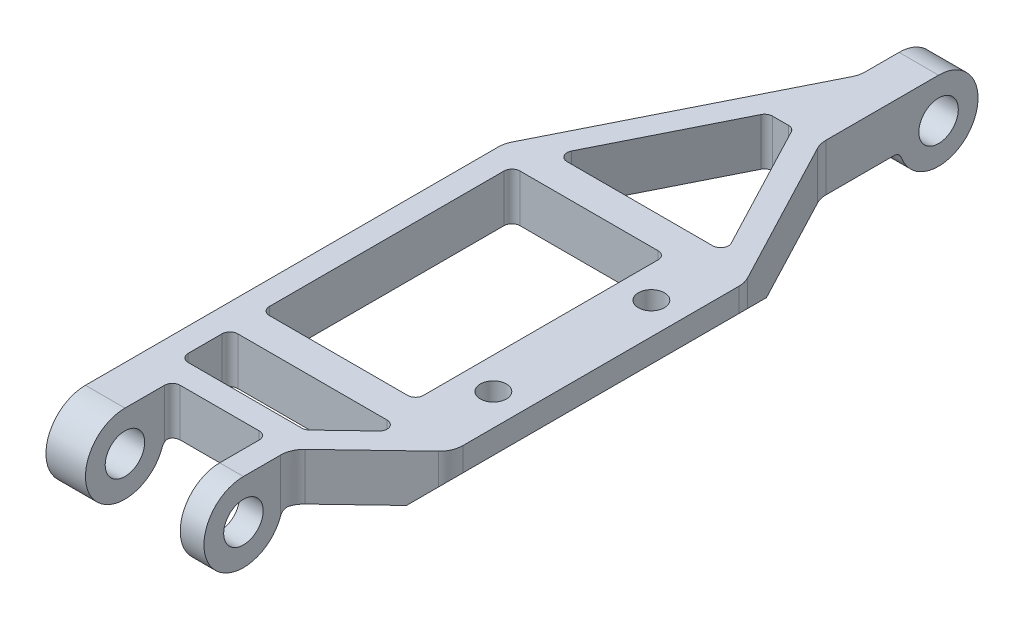
SolidWorks part; units mm, degrees
material "6061 合金"
ref_plane "前视基准面" through (0, 0, 0) normal (0, 0, 1) x (1, 0, 0)
ref_plane "上视基准面" through (0, 0, 0) normal (0, 1, 0) x (1, 0, 0)
ref_plane "右视基准面" through (0, 0, 0) normal (1, 0, 0) x (0, 0, -1)
sketch "草图1" plane through (0, 0, 0) normal (0, 1, 0) x (1, 0, 0)
  line L0 (-22.5, 87) -> (-27.5, 87)
  line L1 (-27.5, 87) -> (-27.5, 77)
  line L3 (-42.5, 47) -> (-42.5, -11)
  line L4 (-42.5, -11) -> (-37.5, -11)
  line L5 (-37.5, -11) -> (-37.5, 0)
  line L6 (-37.5, 0) -> (-25.5, 0)
  line L7 (-22.5, 87) -> (-22.5, 67)
  line L17 (-22.5, 82) -> (-27.5, 82) construction
  line L18 (-37.5, -6) -> (-42.5, -6) construction
  line L19 (-27.5, 77) -> (-42.5, 47)
  line L27 (-25.5, 0) -> (-25.5, -11)
  line L28 (-25.5, -11) -> (-22.5, -11)
  line L34 (-22.5, 67) -> (-12, 47)
  line L35 (-12, 47) -> (-12, 10)
  line L37 (-42.5, 47) -> (-12, 47) construction
  line L49 (-22.5, -11) -> (-22.5, 0)
  line L50 (-22.5, 0) -> (-12, 10)
  point P8 (-17.5098, 12.0064)
  point P10 (0, 0)
  point P11 (-22.5, 3.3726)
  point P12 (-17, 47)
  point P13 (-17.9631, 47)
  point P17 (-9.7565, 10)
  point P18 (-9.7565, 47)
  point P19 (-12, 47.7019)
  dimension "D10" = 10.5
  dimension "D2" = 5
  dimension "D3" = 20
  dimension "D4" = 88
  dimension "D5" = 5
  dimension "D6" = 5
  dimension "D7" = 11
  dimension "D8" = 5
  dimension "D9" = 30.5
  dimension "D11" = 35
  dimension "D12" = 12
  dimension "D13" = 10
  dimension "D14" = 10
  dimension "D15" = 3
extrude "凸台-拉伸1" add sketch "草图1" along normal mid plane 10
sketch "草图3" plane through (0, 5, 0) normal (0, 1, 0) x (1, 0, 0)
  line L4 (-42.5, 45) -> (-12, 45) construction
  line L62 (-42.5, 49) -> (-12, 49) construction
  line L66 (-39.5, 9.2857) -> (-39.5, 3)
  line L69 (-15, 9.2857) -> (-39.5, 9.2857) construction
  line L77 (-15, 13.2857) -> (-39.5, 13.2857) construction
  line L78 (-12, 10) -> (-12, 47) construction
  line L79 (-25.8883, 67) -> (-29.1459, 67)
  line L108 (-42.5, 47) -> (-12, 47) construction
  line L109 (-15, 11.2857) -> (-39.5, 11.2857) construction
  line L118 (-39.5, 45) -> (-20, 45)
  line L123 (-20, 13.2857) -> (-39.5, 13.2857)
  line L124 (-38.1459, 49) -> (-16.4383, 49)
  line L125 (-25.5, 74.2918) -> (-39.5, 46.2918)
  line L126 (-39.5, 46.2918) -> (-39.5, 3)
  line L127 (-39.5, 3) -> (-23.7, 3)
  line L128 (-23.7, 3) -> (-15, 11.2857)
  line L129 (-15, 11.2857) -> (-15, 46.2604)
  line L130 (-15, 46.2604) -> (-25.5, 66.2604)
  line L131 (-29.1459, 67) -> (-38.1459, 49)
  line L132 (-39.5, 45) -> (-39.5, 13.2857)
  line L133 (-39.5, 3) -> (-23.7, 3)
  line L134 (-23.7, 3) -> (-17.1, 9.2857)
  line L135 (-20, 13.2857) -> (-20, 45)
  line L136 (-16.4383, 49) -> (-25.8883, 67)
  line L137 (-17.1, 9.2857) -> (-39.5, 9.2857)
  line L144 (-25.5, 66.2604) -> (-25.5, 74.2918)
  dimension "D2" = 2
  dimension "D4" = 8
  dimension "D3" = 2
  dimension "D1" = 3
extrude "切除-拉伸2" cut sketch "草图3" against normal through all
sketch "草图2" plane through (0, 0, 0) normal (1, 0, 0) x (0, 0, -1)
  line L0 (-1.101, -1) -> (77.101, -1)
  line L4 (-12, 5) -> (-12, -6)
  line L5 (-12, -6) -> (88, -6)
  line L6 (88, -6) -> (88, 5)
  line L9 (-6, 5) -> (-12, 5)
  line L10 (82, 5) -> (88, 5)
  line L11 (-11, 5) -> (-11, -5) construction
  line L12 (-11, -5) -> (0, -5) construction
  line L13 (10, 5) -> (47, 5) construction
  line L14 (-11, 5) -> (0, 5) construction
  line L15 (67, 5) -> (87, 5) construction
  line L16 (87, 5) -> (87, -5) construction
  circle A0 centre (-6, 0) radius 2.5
  circle A1 centre (82, 0) radius 2.5
  arc A2 (-6, 5) -> (-1.101, -1) centre (-6, 0) ccw
  arc A3 (77.101, -1) -> (82, 5) centre (82, 0) ccw
  point P15 (-6, 5)
  point P22 (82.6477, 5)
  dimension "D1" = 5
  dimension "D2" = 1
  dimension "D3" = 1
  dimension "D4" = 6
  dimension "D5" = 1
extrude "切除-拉伸1" cut sketch "草图2" against normal through all both and the other way through all
hole_wizard "M4 螺纹孔1" positions "草图5" profile "草图6" tap size "M4" standard "GB" end condition through all
sketch "草图5" plane through (0, 5, 0) normal (0, 1, 0) x (1, 0, 0)
  line L0 (-16, 19.1429) -> (-16, 39.1429) construction
  line L4 (-20, 13.2857) -> (-20, 45) construction
  line L5 (-12, 10) -> (-12, 47) construction
  point P0 (-16, 39.1429)
  point P2 (-16, 19.1429)
  point P15 (-20, 29.1429)
  point P16 (-16, 29.1429)
  dimension "D1" = 4
  dimension "D2" = 20
sketch "草图6" plane through (-16, 5, -39.1429) normal (1, 0, 0) x (0, 0, 1)
  line L0 (0, 0) -> (0, 10)
  line L1 (0, 10) -> (1.65, 10)
  line L2 (1.65, 10) -> (1.65, 0)
  line L5 (1.65, 0) -> (0, 0)
  line L11 (0, -6.35) -> (0, 107.95) construction
  dimension "通孔螺纹孔钻头直径" = 3.3
  dimension "通孔螺纹孔钻头深度" = 10
cosmetic thread "孔螺蚊线1" parameters "D2"=4
cosmetic thread "孔螺蚊线2" parameters "D2"=4
fillet "圆角1" radius 1 15 edges at (-25, -1, -77.101) (-24, -1, 1.101) (-40, -1, 1.101) (-20, 2, -45) (-20, 2, -13.2857) (-39.5, 2, -13.2857) (-16.4383, 2, -49) (-38.1459, 2, -49) (-39.5, 2, -9.2857) (-17.1, 2, -9.2857) (-23.7, 2, -3) (-39.5, 2, -3) (-39.5, 2, -45) (-29.1459, 2, -67) (-25.8883, 2, -67)
fillet "圆角2" radius 1 2 edges at (-37.5, 2, 0) (-25.5, 2, 0)
fillet "圆角3" radius 3 6 edges at (-42.5, 2, -47) (-27.5, 1.877, -77) (-22.5, 2, -67) (-22.5, 2, 0) (-12, 2, -47) (-12, 2, -10)
chamfer "倒角1" distance 3 angle 45 1 edges at (-12, -1, -28.773) tangent propagation no
